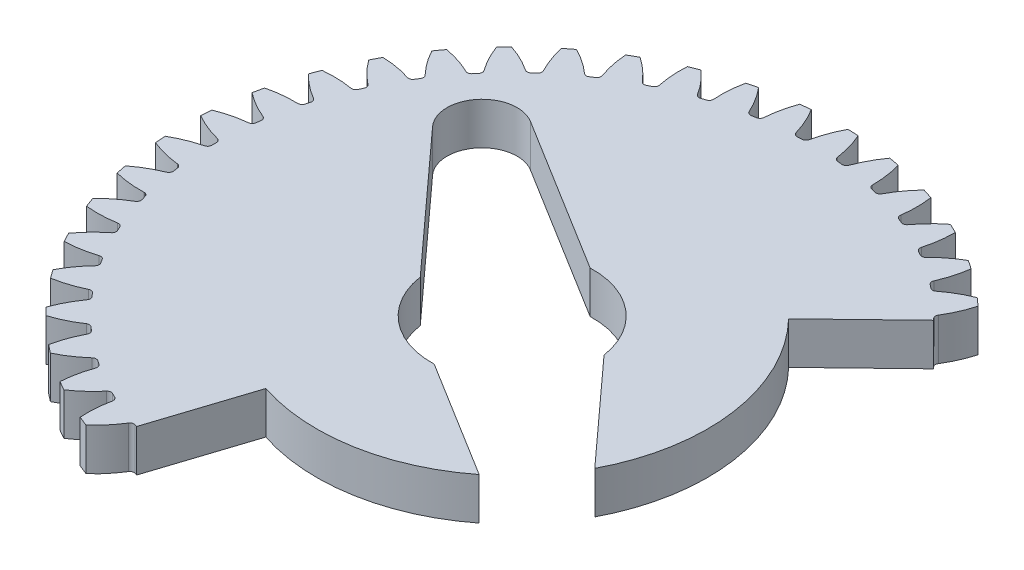
SolidWorks part; units mm, degrees
ref_plane "Alzado" through (0, 0, 0) normal (0, 0, 1) x (1, 0, 0)
ref_plane "Planta" through (0, 0, 0) normal (0, 1, 0) x (1, 0, 0)
ref_plane "Vista lateral" through (0, 0, 0) normal (1, 0, 0) x (0, 0, -1)
sketch "Croquis1" plane through (0, 0, 0) normal (0, 1, 0) x (1, 0, 0)
  line L0 (0, 0) -> (0, 18.2727) construction
  line L1 (0, 22.5) -> (7.2315, 19.8679) construction
  line L2 (0, 0) -> (0.6441, 18.4397) construction
  line L3 (1.5698, 22.4452) -> (-5.8277, 20.324) construction
  circle A0 centre (0, 0) radius 21.143 construction
  circle A1 centre (0, 0) radius 21.25 construction
  circle A2 centre (0, 0) radius 22.5 construction
  circle A3 centre (0, 0) radius 23.5 construction
  arc A4 (0.4447, 23.4958) -> (-0.3395, 21.2473) centre (7.2315, 19.8679) ccw
  arc A5 (1.1957, 23.4696) -> (1.8211, 21.1718) centre (-5.8277, 20.324) cw
  dimension "De" = 47
  dimension "Dp" = 45
  dimension "Di" = 42.5
  dimension "Ct" = 42.2861
  dimension "E" = 1.5708
sketch "Croquis3" plane through (0, 0, 0) normal (0, 1, 0) x (1, 0, 0)
  circle A0 centre (0, 0) radius 23.5 construction
  arc A1 (1.8211, 21.1718) -> (1.1957, 23.4696) centre (-5.8277, 20.324) ccw construction
  circle A2 centre (0, 0) radius 21.25 construction
  arc A3 (0.4447, 23.4958) -> (-0.3395, 21.2473) centre (7.2315, 19.8679) ccw construction
  arc A4 (1.1957, 23.4696) -> (0.4447, 23.4958) centre (0, 0) ccw
  arc A5 (1.8211, 21.1718) -> (1.1957, 23.4696) centre (-5.8277, 20.324) ccw
  arc A6 (-0.3395, 21.2473) -> (1.8211, 21.1718) centre (0, 0) ccw
  arc A7 (0.4447, 23.4958) -> (-0.3395, 21.2473) centre (7.2315, 19.8679) ccw
extrude "Saliente-Extruir1" add sketch "Croquis3" along normal blind 3 contours A6 A5 A4 A7
fillet "Redondeo1" radius 0.3 2 edges at (-0.3395, 1.5, -21.2473) (1.8211, 1.5, -21.1718)
pattern_circular "MatrizC1" count 45 over 360 about axis through (0, 3, 0) along (0, 1, 0) of "Saliente-Extruir1", "Redondeo1"
sketch "Croquis4" plane through (0, 3, 0) normal (0, 1, 0) x (1, 0, 0)
  circle A0 centre (0, 0) radius 2.5
  dimension "D1" = 5
extrude "Cortar-Extruir1" cut sketch "Croquis4" against normal blind 3
sketch "Croquis5" plane through (0, 0, 0) normal (0, -1, 0) x (1, 0, 0)
  line L4 (-5.6843, 0.8665) -> (-14.5379, -8.865)
  line L5 (-11.3726, -12.6729) -> (-0.1869, -5.747)
  line L6 (5.6843, -0.8665) -> (14.5379, 8.865)
  line L7 (11.3726, 12.6729) -> (0.1869, 5.747)
  line L8 (-5.6843, 0.8665) -> (-14.5379, -8.865)
  line L9 (-11.3726, -12.6729) -> (-0.1869, -5.747)
  line L10 (5.6843, -0.8665) -> (14.5379, 8.865)
  line L11 (11.3726, 12.6729) -> (0.1869, 5.747)
  arc A4 (0.1869, 5.747) -> (-5.6843, 0.8665) centre (0, 0) ccw
  arc A5 (-14.5379, -8.865) -> (-11.3726, -12.6729) centre (-12.6887, -10.5474) ccw
  arc A6 (-0.1869, -5.747) -> (5.6843, -0.8665) centre (0, 0) ccw
  arc A7 (14.5379, 8.865) -> (11.3726, 12.6729) centre (12.6887, 10.5474) ccw
  arc A8 (0.1869, 5.747) -> (-5.6843, 0.8665) centre (0, 0) ccw
  arc A9 (-14.5379, -8.865) -> (-11.3726, -12.6729) centre (-12.6887, -10.5474) ccw
  arc A10 (-0.1869, -5.747) -> (5.6843, -0.8665) centre (0, 0) ccw
  arc A11 (14.5379, 8.865) -> (11.3726, 12.6729) centre (12.6887, 10.5474) ccw
  dimension "D1" = 0
extrude "Cortar-Extruir2" cut sketch "Croquis5" against normal blind 10
sketch "Croquis8" plane through (0, 3, 0) normal (0, 1, 0) x (1, 0, 0)
  line L0 (-4.3079, -13.258) -> (-6.5668, -20.2099)
  line L1 (-6.5668, -20.2099) -> (-8.0565, -24.7948)
  line L4 (10.0279, 9.6837) -> (15.2861, 14.7614)
  line L5 (15.2861, 14.7614) -> (18.7539, 18.1102)
  arc A2 (-8.0565, -24.7948) -> (18.7539, 18.1102) centre (0, 0) ccw
  arc A3 (-4.3079, -13.258) -> (10.0279, 9.6837) centre (0, 0) ccw
  arc A4 (-6.7214, -20.159) -> (-6.4117, -20.2596) centre (0, 0) ccw construction
  arc A6 (15.3987, 14.6438) -> (15.1725, 14.8781) centre (0, 0) ccw construction
extrude "Cortar-Extruir6" cut sketch "Croquis8" against normal blind 10
equation "\"M\"= 1"
equation "\"N\"= 45"
equation "\"a\"= 20"
equation "\"De@Croquis1\"= \"M\" * ( \"N\" + 2 )"
equation "\"Dp@Croquis1\"= \"M\" * \"N\""
equation "\"Di@Croquis1\" = \"Dp@Croquis1\" - \"M\" * 2.5"
equation "\"Ct@Croquis1\"= \"Dp@Croquis1\" * 0.93969"
equation "\"E@Croquis1\"= \"M\" * 1.5708"
equation "\"D1@Redondeo1\"=\"M\"*0.3"
equation "\"D1@MatrizC1\"=\"N\""
